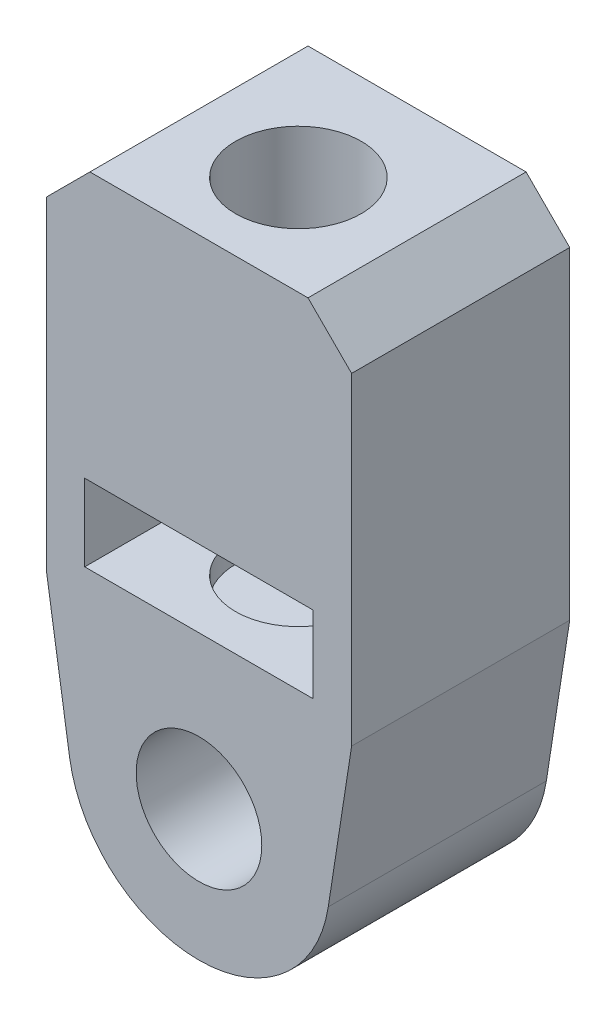
SolidWorks part; units mm, degrees
ref_plane "Front Plane" through (0, 0, 0) normal (0, 0, 1) x (1, 0, 0)
ref_plane "Top Plane" through (0, 0, 0) normal (0, 1, 0) x (1, 0, 0)
ref_plane "Right Plane" through (0, 0, 0) normal (1, 0, 0) x (0, 0, -1)
sketch "Sketch1" plane through (0, 0, 0) normal (0, 0, 1) x (1, 0, 0)
  line L0 (-5.5562, 4.7625) -> (-5.5562, 18.0975)
  line L1 (-5.5562, 18.0975) -> (5.5562, 18.0975)
  line L2 (5.5562, 18.0975) -> (5.5562, 4.7625)
  line L3 (-5.5562, 4.7625) -> (-4.7065, -0.7284)
  line L4 (4.7065, -0.7284) -> (5.5562, 4.7625)
  circle A1 centre (0, 0) radius 2.286
  arc A2 (-4.7065, -0.7284) -> (4.7065, -0.7284) centre (0, 0) ccw
  point P8 (0, 0)
  point P9 (0, 0)
  point P10 (0, 18.0975)
  dimension "D1" = 9.525
  dimension "D2" = 4.572
  dimension "D3" = 13.335
  dimension "D4" = 11.1125
  dimension "D5" = 4.7625
extrude "Boss-Extrude1" add sketch "Sketch1" along normal up to surface (7.9375 mm away)
sketch "Sketch2" plane through (0, 18.0975, 0) normal (0, 1, 0) x (1, 0, 0)
  circle A1 centre (0, -4.3188) radius 2.286
  circle A2 centre (0, -4.3188) radius 1.7525 construction
  dimension "D1" = 4.572
extrude "Cut-Extrude1" cut sketch "Sketch2" against normal offset from surface (13.335 mm away) 4.7625 up to plane "Top Plane"
sketch "Sketch3" plane through (0, 4.7625, 0) normal (0, 1, 0) x (1, 0, 0)
  line L11 (5.5562, -7.9375) -> (-5.5562, -7.9375) construction
  line L12 (-1.9064, -1.0168) -> (-4.1565, -4.9141)
  line L16 (4.1565, -4.9141) -> (1.9064, -1.0168)
  line L17 (1.9064, -1.0168) -> (-1.9064, -1.0168)
  line L18 (-4.1565, -4.9141) -> (-4.1565, -7.9375)
  line L19 (-4.1565, -7.9375) -> (4.1565, -7.9375)
  line L20 (4.1565, -7.9375) -> (4.1565, -4.9141)
  line L22 (-1.9064, -7.6208) -> (0, -7.6208) [skipped]
  line L23 (-3.8128, -4.3188) -> (-2.8596, -5.9698) [skipped]
  line L24 (2.1818, -7.1438) -> (2.8596, -5.9698) [skipped]
  circle A0 centre (0, -4.3188) radius 3.302 construction
  dimension "D1" = 6.604
extrude "Cut-Extrude2" cut sketch "Sketch3" along normal blind 2.794 from offset 0.7937
chamfer "Chamfer1" distance 1.5875 angle 45 2 edges at (5.5562, 18.0975, 3.9688) (-5.5562, 18.0975, 3.9688)
